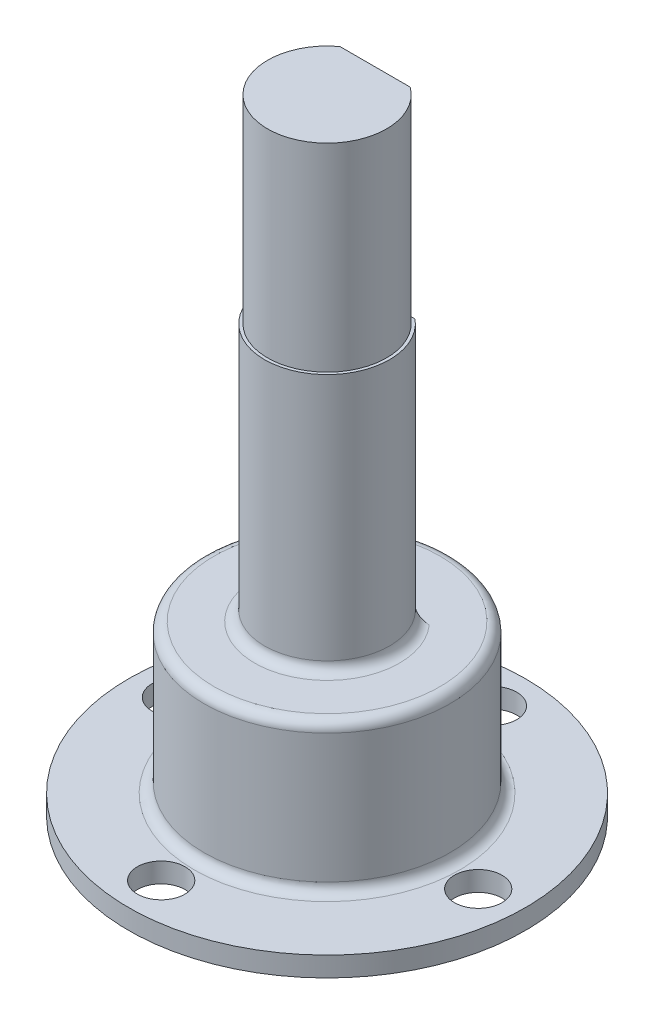
SolidWorks part; units mm, degrees
material "ABS"
ref_plane "Plan de face" through (0, 0, 0) normal (0, 0, 1) x (1, 0, 0)
ref_plane "Plan de dessus" through (0, 0, 0) normal (0, 1, 0) x (1, 0, 0)
ref_plane "Plan de droite" through (0, 0, 0) normal (1, 0, 0) x (0, 0, -1)
sketch "Esquisse2" plane through (0, 0, 0) normal (0, 0, 1) x (1, 0, 0)
  line L0 (0, 31.5) -> (3, 31.5)
  line L3 (6.2, 3) -> (6.2, 1)
  line L4 (6.2, 1) -> (10, 1)
  line L5 (10, 1) -> (10, 0)
  line L6 (10, 0) -> (4.5, 0)
  line L7 (4.5, 0) -> (4.5, 5)
  line L8 (4.5, 5) -> (0, 5)
  line L9 (0, 5) -> (0, 31.5)
  line L11 (3.15, 21.5) -> (3.15, 8.5)
  line L12 (3.15, 8.5) -> (6.2, 8.5)
  line L13 (6.2, 3) -> (6.2, 8.5)
  line L14 (3.15, 21.5) -> (3, 21.5)
  line L15 (3, 21.5) -> (3, 31.5)
  point P2 (1.5, 31.5)
  dimension "D1" = 10
  dimension "D2" = 31.5
  dimension "D3" = 0
  dimension "D4" = 1
  dimension "D5" = 4.5
  dimension "D6" = 2
  dimension "D7" = 8.5
  dimension "D8" = 5
  dimension "D9" = 3.15
  dimension "D10" = 0
  dimension "D11" = 3
  dimension "D12" = 1.7
  dimension "D13" = 10
revolve "Révolution2" add sketch "Esquisse2" angle 360 about L9
sketch "Esquisse3" plane through (0, 31.5, 0) normal (0, 1, 0) x (1, 0, 0)
  line L1 (-3.6413, 2.4219) -> (2.9365, 2.4219)
  line L2 (-3.6413, 2.4219) -> (-3.6413, 3.808)
  line L3 (-3.6413, 3.808) -> (2.9365, 3.808)
  line L4 (2.9365, 2.4219) -> (2.9365, 3.808)
  dimension "D1" = 6.5779
extrude "Enlèv. mat.-Extru.1" cut sketch "Esquisse3" against normal up to surface (23 mm away) contours L4 L3 L2 L1 up to face at (0, 8.5, -3.15)
hole_wizard "Dégagement M21" positions "Esquisse4" profile "Esquisse5" hole size "M2" standard "Ansi Metric" end condition up to next
sketch "Esquisse4" plane through (0, 1, 0) normal (0, 1, 0) x (1, 0, 0)
  circle A0 centre (0, 0) radius 8 construction
  point P0 (0.3713, 7.9914)
  dimension "D1" = 16
sketch "Esquisse5" plane through (0.3713, 1, -7.9914) normal (1, 0, 0) x (0, 0, 1)
  line L0 (0, 0) -> (0, 1.001)
  line L1 (0, 1.001) -> (1.2, 1.001)
  line L2 (1.2, 1.001) -> (1.2, 0)
  line L5 (1.2, 0) -> (0, 0)
  line L11 (0, -6.35) -> (0, 107.95) construction
  dimension "Diamètre du perçage jusqu'au prochain" = 2.4
  dimension "Profondeur du perçage jusqu'au prochain" = 1.001
pattern_circular "Répétition circulaire1" count 4 over 360 about axis through (0, 1, 0) along (0, -1, 0) of "Dégagement M21"
fillet "Fillet1" radius 0.5 3 edges at (0, 8.5, -6.2) (0, 1, -6.2) (0, 8.5, 3.15)
